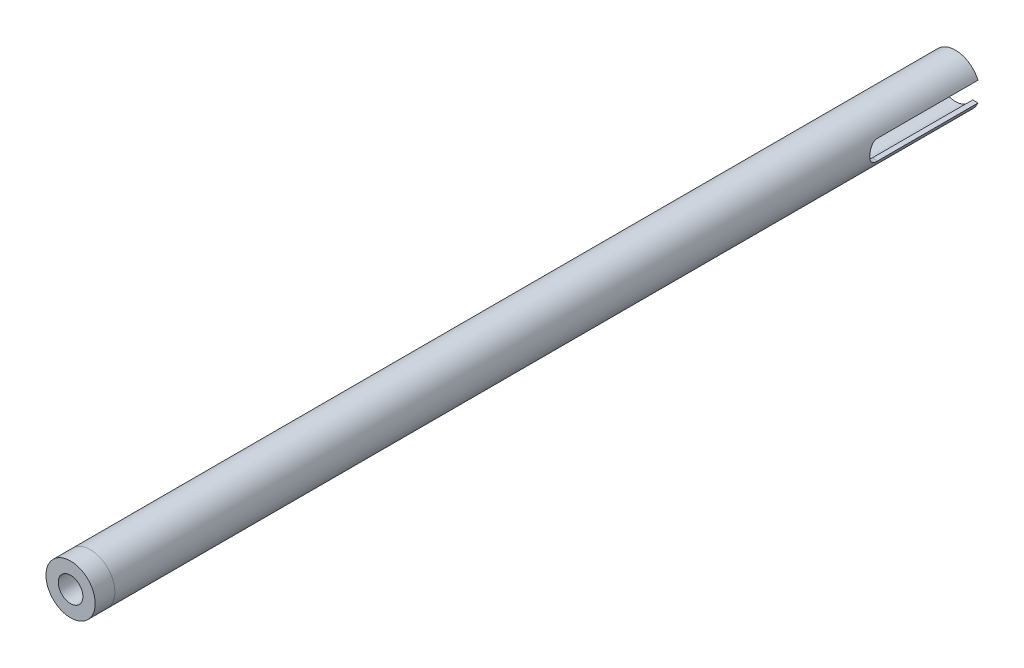
SolidWorks part; units mm, degrees
ref_plane "Front Plane" through (0, 0, 0) normal (0, 0, 1) x (1, 0, 0)
ref_plane "Top Plane" through (0, 0, 0) normal (0, 1, 0) x (1, 0, 0)
ref_plane "Right Plane" through (0, 0, 0) normal (1, 0, 0) x (0, 0, -1)
sketch "Axis" plane through (0, 0, 0) normal (0, 1, 0) x (1, 0, 0)
  line L0 (0, 0) -> (0, 285.235) construction
  line L1 (0, 0) -> (0, -34.925) construction
  line L2 (0, 285.235) -> (-7.9375, 285.235) construction
  line L3 (0, 310.8809) -> (-28.8739, 217.5896) construction
  dimension "D1" = 34.925
  dimension "D2" = 7.9375
sketch "Sketch1" plane through (0, 0, 0) normal (0, 0, 1) x (1, 0, 0)
  line L0 (-7.9375, 0) -> (7.9375, 0) construction
  line L1 (-7.2748, 3.175) -> (7.2748, 3.175)
  line L2 (-7.2748, -3.175) -> (7.2748, -3.175)
  circle A0 centre (0, 0) radius 7.9375
  circle A1 centre (0, 0) radius 6.4135
  circle A2 centre (0, 0) radius 3.9688
  dimension "D1" = 15.875
  dimension "D3" = 7.9375
  dimension "D2" = 1.524
  dimension "D4" = 6.35
extrude "Threaded insert 1-1" add sketch "Sketch1" against normal blind 6.35 contours A2 L1 A1 | A1 L1 A0 | A2 L0 A1 L1 | A1 L0 A0 L1 | L0 A1 L2 A0 | L0 A2 L2 A1 | A2 L2 A1 | A1 L2 A0 | L0 A1 L2 A2 | L0 A0 L2 A1 | A0 L0 A1 L1 | A1 L0 A2 L1 region at (4.7887, 1.6543, 0) region at (4.7887, -1.6543, 0) region at (6.9234, 1.6163, 0) region at (6.9234, -1.6163, 0) region at (-4.7887, -1.6543, 0) region at (-4.7887, 1.6543, 0) region at (0, 4.6159, 0) region at (0, -4.6159, 0) region at (0, 6.5666, 0) region at (6.4237, -3.3281, 0) region at (-6.9234, -1.6163, 0) region at (-6.9234, 1.6163, 0)
extrude "Threaded insert 1-2" add sketch "Sketch1<3>" against normal blind 9.525 from surface contours A2 L1 A1 | A2 L0 A1 L1 | L0 A2 L2 A1 | A2 L2 A1 | L0 A1 L2 A2 | A1 L0 A2 L1 region at (4.7887, 1.6543, 0) region at (4.7887, -1.6543, 0) region at (-4.7887, -1.6543, 0) region at (-4.7887, 1.6543, 0) region at (0, 4.6159, 0) region at (0, -4.6159, 0) starting at face at (7.9375, 0, -6.35)
sketch "Sketch1<3>" plane through (0, 0, 0) normal (0, 0, 1) x (1, 0, 0) same geometry as "Sketch1"
extrude "A-arm tube" add sketch "Sketch1<4>" against normal up to vertex (285.235 mm away) from surface separate body contours A1 L1 A0 | A1 L0 A0 L1 | L0 A1 L2 A0 | A1 L2 A0 | L0 A0 L2 A1 | A0 L0 A1 L1 region at (6.9234, 1.6163, 0) region at (6.9234, -1.6163, 0) region at (0, 6.5666, 0) region at (6.4237, -3.3281, 0) region at (-6.9234, -1.6163, 0) region at (-6.9234, 1.6163, 0) up to point (0, 0, -285.235) starting at face at (6.4135, 0, -6.35)
sketch "Sketch1<4>" plane through (0, 0, 0) normal (0, 0, 1) x (1, 0, 0) same geometry as "Sketch1"
extrude "Apex slot" cut sketch "Sketch1<5>" along normal blind 35.56 from surface contours A0 L0 A1 L1 | L0 A0 L2 A1 | A1 L0 A0 L1 | L0 A1 L2 A0 region at (6.9234, 1.6163, 0) region at (6.9234, -1.6163, 0) region at (-6.9234, -1.6163, 0) region at (-6.9234, 1.6163, 0) starting at face at (6.4135, 0, -285.235)
sketch "Sketch1<5>" plane through (0, 0, 0) normal (0, 0, 1) x (1, 0, 0) same geometry as "Sketch1"
fillet "Fillet1" radius 3.175 4 edges at (-6.4237, 3.175, -249.675) (-6.4237, -3.175, -249.675) (6.4237, -3.175, -249.675) (6.4237, 3.175, -249.675)
equation "\"tube diameter\"= 5 / 8"
equation "\"tube thickness\"= .06"
equation "\"apex thickness\"= .25"
equation "\"tube slot\"= 1.4"
equation "\"D1@Sketch1\"=\"tube diameter\""
equation "\"D2@Sketch1\"=\"tube thickness\""
equation "\"threaded insert hole\"= .3125"
equation "\"D3@Sketch1\"=\"threaded insert hole\""
equation "\"D4@Sketch1\"=\"apex thickness\""
equation "\"D1@Apex slot\" = \"tube slot\""
equation "\"D1@Fillet1\"=\"apex thickness\"/2"
equation "\"D2@Axis\"=\"tube diameter\"/2"
